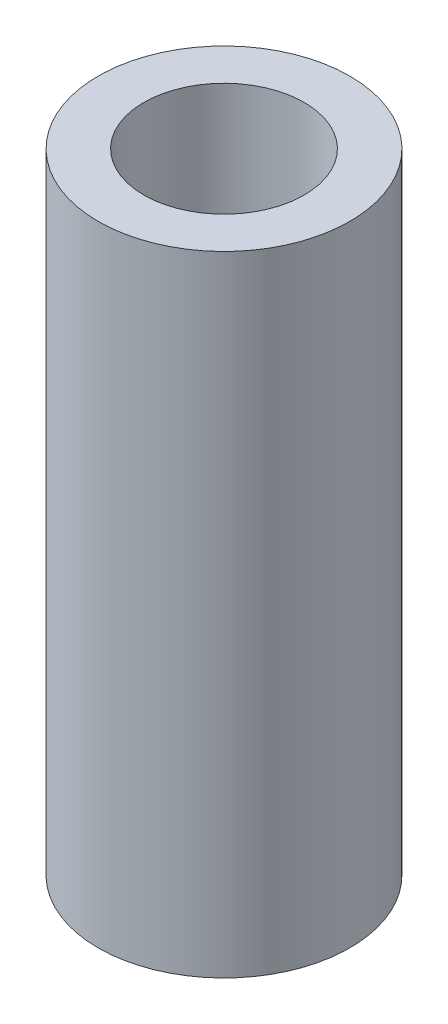
SolidWorks part; units mm, degrees
ref_plane "前视基准面" through (0, 0, 0) normal (0, 0, 1) x (1, 0, 0)
ref_plane "上视基准面" through (0, 0, 0) normal (0, 1, 0) x (1, 0, 0)
ref_plane "右视基准面" through (0, 0, 0) normal (1, 0, 0) x (0, 0, -1)
sketch "草图1" plane through (0, 0, 0) normal (0, 1, 0) x (1, 0, 0)
  circle A0 centre (0, 0) radius 2.55
  circle A1 centre (0, 0) radius 4
extrude "凸台-拉伸1" add sketch "草图1" along normal blind 20
